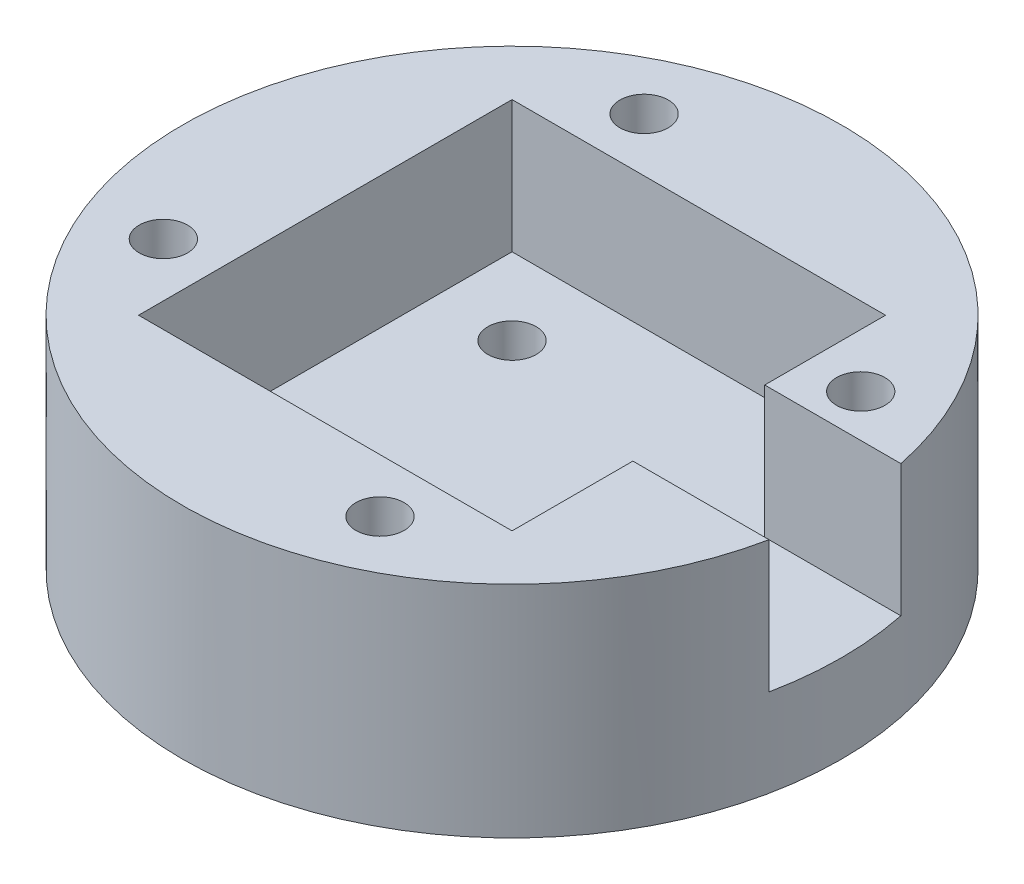
SolidWorks part; units mm, degrees
ref_plane "Front Plane" through (0, 0, 0) normal (0, 0, 1) x (1, 0, 0)
ref_plane "Top Plane" through (0, 0, 0) normal (0, 1, 0) x (1, 0, 0)
ref_plane "Right Plane" through (0, 0, 0) normal (1, 0, 0) x (0, 0, -1)
sketch "Sketch1" plane through (0, 0, 0) normal (0, 1, 0) x (1, 0, 0)
  line L0 (-15, 0) -> (15, 0)
  line L1 (8.5, -8.5) -> (-8.5, -8.5)
  line L2 (8.5, -8.5) -> (8.5, 8.5)
  line L3 (8.5, 8.5) -> (-8.5, 8.5)
  line L4 (-8.5, -8.5) -> (-8.5, 8.5)
  line L5 (8.5, -8.5) -> (-8.5, 8.5) construction
  line L6 (8.5, 8.5) -> (-8.5, -8.5) construction
  line L7 (5, -5) -> (-5, -5)
  line L8 (5, -5) -> (5, 5)
  line L9 (5, 5) -> (-5, 5)
  line L10 (-5, -5) -> (-5, 5)
  line L11 (5, -5) -> (-5, 5) construction
  line L12 (5, 5) -> (-5, -5) construction
  line L14 (21.5, -3) -> (8.5, -3)
  line L15 (21.5, -3) -> (21.5, 3)
  line L16 (21.5, 3) -> (8.5, 3)
  line L17 (8.5, -3) -> (8.5, 3)
  line L18 (21.5, -3) -> (8.5, 3) construction
  line L19 (21.5, 3) -> (8.5, -3) construction
  circle A0 centre (0, 0) radius 15
  circle A1 centre (-5, 5) radius 1.1
  circle A2 centre (-5, -5) radius 1.1
  circle A3 centre (10.9405, 4.9301) radius 1.1
  point P18 (0, 0)
  dimension "D2" = 30
  dimension "D5" = 2.2
  dimension "D6" = 2.2
  dimension "D7" = 2.2
  dimension "D8" = 12
  dimension "D9" = 4.25
  dimension "D1" = 17
  dimension "D3" = 17
  dimension "D4" = 10
  dimension "D10" = 6
extrude "Boss-Extrude1" add sketch "Sketch1" along normal blind 10 contours L16 A0 L0 L4 L3 L2 A3 | L0 A0 L14 L2 L1 L4 | L14 A0 L0 L2 | L0 A0 L16 L2 | A1 L9 L8 L0 L2 L3 L4 L10 | L9 A1 L10 | A1 L10 L0 L8 L9 | L10 A1 L9 | A2 L10 L0 L4 L1 L2 L8 L7 | L10 A2 L7 | L7 A2 L10 | A2 L7 L8 L0 L10 | A3 region at (-1.4318, 0, -8.5439) region at (-11.75, 0, 0.3327) region at (0.1604, 0, -5.1766) region at (0.1604, 0, 5.1766) region at (11.7003, 0, -1.4882) region at (11.7003, 0, 1.4882) region at (0.0878, 0, -2.4606) region at (0.0878, 0, 2.4606) region at (-4.5331, 0, 4.5331) region at (-5.1556, 0, 5.1556) region at (-5.1556, 0, -5.1556) region at (-4.5331, 0, -4.5331) region at (10.9405, 0, -4.9301)
extrude "accel cutout" cut sketch "Sketch1<3>" along normal blind 6 from offset 4 contours A1 L9 L8 L0 L2 L3 L4 L10 | A1 L10 L0 L8 L9 | A2 L7 L8 L0 L10 | A2 L10 L0 L4 L1 L2 L8 L7 | L0 A0 L16 L2 | L14 A0 L0 L2 region at (0.1604, 0, -5.1766) region at (0.1604, 0, 5.1766) region at (11.7003, 0, -1.4882) region at (11.7003, 0, 1.4882) region at (0.0878, 0, -2.4606) region at (0.0878, 0, 2.4606)
sketch "Sketch1<3>" plane through (0, 0, 0) normal (0, 1, 0) x (1, 0, 0) same geometry as "Sketch1"
extrude "accel mount holes" cut sketch "Sketch1<4>" along normal through all contours A1 | A2
sketch "Sketch1<4>" plane through (0, 0, 0) normal (0, 1, 0) x (1, 0, 0) same geometry as "Sketch1"
sketch "Sketch2" plane through (0, 0, 0) normal (0, 1, 0) x (1, 0, 0)
  circle A0 centre (0, 0) radius 5
  dimension "D1" = 10
extrude "rear thread insert" cut sketch "Sketch2" along normal blind 3
extrude "layerscrew holes" cut sketch "Sketch1<5>" along normal through all contours A3 region at (10.9405, 0, -4.9301)
sketch "Sketch1<5>" plane through (0, 0, 0) normal (0, 1, 0) x (1, 0, 0) same geometry as "Sketch1"
pattern_circular "layerscrew holes more" count 4 every 90 about axis through (0, 10, 0) along (0, -1, 0) of "layerscrew holes"
